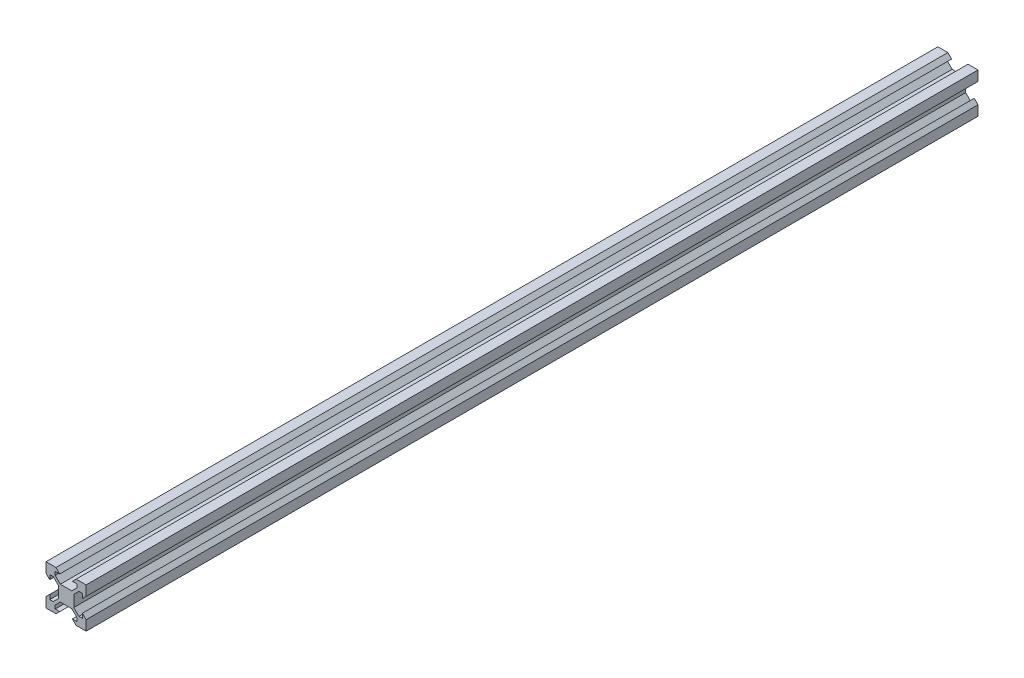
SolidWorks part; units mm, degrees
ref_plane "Front Plane" through (0, 0, 0) normal (0, 0, 1) x (1, 0, 0)
ref_plane "Top Plane" through (0, 0, 0) normal (0, 1, 0) x (1, 0, 0)
ref_plane "Right Plane" through (0, 0, 0) normal (1, 0, 0) x (0, 0, -1)
sketch "Sketch1" plane through (0, 0, 0) normal (0, 0, 1) x (1, 0, 0)
  line L0 (0, 0) -> (0, 10) construction
  line L1 (0, 0) -> (10, 0) construction
  line L2 (-2.8601, 3.85) -> (2.8601, 3.85)
  line L3 (5.4, 6.3899) -> (5.4, 8.125)
  line L4 (5.4, 8.125) -> (3.15, 8.125)
  line L5 (3.15, 8.125) -> (5.025, 10)
  line L6 (5.025, 10) -> (10, 10)
  line L7 (0, 0) -> (10, 10) construction
  line L8 (5.4, 6.3899) -> (2.8601, 3.85)
  line L9 (6.3899, 5.4) -> (3.85, 2.8601)
  line L10 (10, 5.025) -> (10, 10)
  line L11 (8.125, 3.15) -> (10, 5.025)
  line L12 (8.125, 5.4) -> (8.125, 3.15)
  line L13 (6.3899, 5.4) -> (8.125, 5.4)
  line L14 (3.85, -2.8601) -> (3.85, 2.8601)
  line L15 (6.3899, -5.4) -> (8.125, -5.4)
  line L16 (8.125, -5.4) -> (8.125, -3.15)
  line L17 (8.125, -3.15) -> (10, -5.025)
  line L18 (10, -5.025) -> (10, -10)
  line L19 (6.3899, -5.4) -> (3.85, -2.8601)
  line L20 (5.4, -6.3899) -> (2.8601, -3.85)
  line L21 (5.025, -10) -> (10, -10)
  line L22 (3.15, -8.125) -> (5.025, -10)
  line L23 (5.4, -8.125) -> (3.15, -8.125)
  line L24 (5.4, -6.3899) -> (5.4, -8.125)
  line L25 (-2.8601, -3.85) -> (2.8601, -3.85)
  line L26 (-5.4, -6.3899) -> (-5.4, -8.125)
  line L27 (-5.4, -8.125) -> (-3.15, -8.125)
  line L28 (-3.15, -8.125) -> (-5.025, -10)
  line L29 (-5.025, -10) -> (-10, -10)
  line L30 (-5.4, -6.3899) -> (-2.8601, -3.85)
  line L31 (-6.3899, -5.4) -> (-3.85, -2.8601)
  line L32 (-10, -5.025) -> (-10, -10)
  line L33 (-8.125, -3.15) -> (-10, -5.025)
  line L34 (-8.125, -5.4) -> (-8.125, -3.15)
  line L35 (-6.3899, -5.4) -> (-8.125, -5.4)
  line L36 (-3.85, -2.8601) -> (-3.85, 2.8601)
  line L37 (-6.3899, 5.4) -> (-8.125, 5.4)
  line L38 (-8.125, 5.4) -> (-8.125, 3.15)
  line L39 (-8.125, 3.15) -> (-10, 5.025)
  line L40 (-10, 5.025) -> (-10, 10)
  line L41 (-6.3899, 5.4) -> (-3.85, 2.8601)
  line L42 (-5.4, 6.3899) -> (-2.8601, 3.85)
  line L43 (-5.025, 10) -> (-10, 10)
  line L44 (-3.15, 8.125) -> (-5.025, 10)
  line L45 (-5.4, 8.125) -> (-3.15, 8.125)
  line L46 (-5.4, 6.3899) -> (-5.4, 8.125)
  point P19 (3.85, 0)
  point P31 (0, -3.85)
  point P32 (0, 3.85)
  point P52 (-3.85, 0)
  dimension "D1" = 10.8
  dimension "D2" = 6.15
  dimension "D4" = 10
  dimension "D5" = 1.4
  dimension "D6" = 6.3
  dimension "D7" = 45
  dimension "D8" = 16.25
extrude "Boss-Extrude1" add sketch "Sketch1" against normal blind 444.5
equation "\"length\" = 444.5"
equation "\"D1@Boss-Extrude1\"=\"length\""
